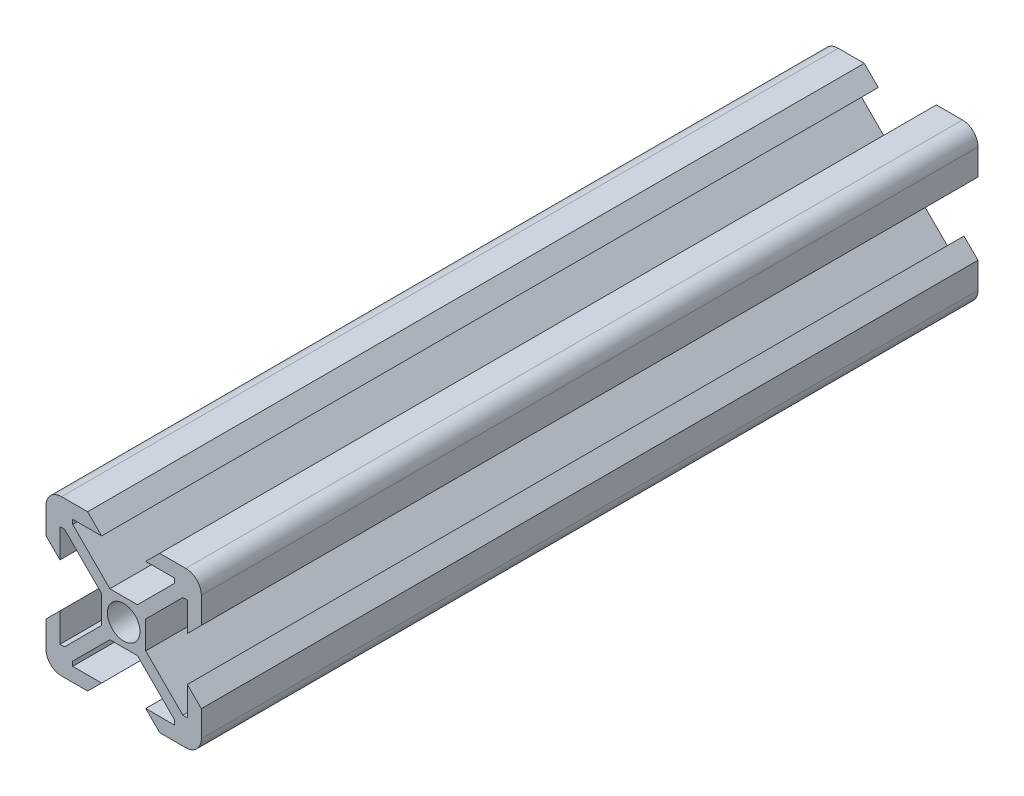
SolidWorks part; units mm, degrees
ref_plane "Front Plane" through (0, 0, 0) normal (0, 0, 1) x (1, 0, 0)
ref_plane "Top Plane" through (0, 0, 0) normal (0, 1, 0) x (1, 0, 0)
ref_plane "Right Plane" through (0, 0, 0) normal (1, 0, 0) x (0, 0, -1)
sketch "Sketch1" plane through (0, 0, 0) normal (0, 0, 1) x (1, 0, 0)
  line L0 (0, 10) -> (0, -2.84) construction
  line L1 (8, 10) -> (4.64, 10)
  line L2 (10, 4.64) -> (8.2, 2.84)
  line L3 (8.2, 2.84) -> (8.2, 6.56)
  line L4 (8.2, 6.56) -> (6.56, 6.56)
  line L5 (6.56, 6.56) -> (2.84, 2.84)
  line L6 (10, 4.64) -> (10, 8)
  line L7 (2.84, -2.84) -> (-2.84, -2.84)
  line L8 (2.84, -2.84) -> (2.84, 2.84)
  line L9 (2.84, 2.84) -> (-2.84, 2.84)
  line L10 (-2.84, -2.84) -> (-2.84, 2.84)
  line L11 (2.84, -2.84) -> (-2.84, 2.84) construction
  line L12 (2.84, 2.84) -> (-2.84, -2.84) construction
  line L13 (-4.64, 10) -> (-2.84, 8.2)
  line L14 (-2.84, 8.2) -> (-6.56, 8.2)
  line L15 (-6.56, 8.2) -> (-6.56, 6.56)
  line L16 (-6.56, 6.56) -> (-2.84, 2.84)
  line L17 (6.56, 6.56) -> (2.84, 2.84)
  line L18 (6.56, 8.2) -> (6.56, 6.56)
  line L19 (2.84, 8.2) -> (6.56, 8.2)
  line L20 (4.64, 10) -> (2.84, 8.2)
  line L21 (-4.64, 10) -> (-8, 10)
  line L22 (6.56, -6.56) -> (2.84, -2.84)
  line L23 (8.2, -6.56) -> (6.56, -6.56)
  line L24 (8.2, -2.84) -> (8.2, -6.56)
  line L25 (10, -4.64) -> (8.2, -2.84)
  line L26 (10, -8) -> (10, -4.64)
  line L27 (4.64, -10) -> (2.84, -8.2)
  line L28 (2.84, -8.2) -> (6.56, -8.2)
  line L29 (6.56, -8.2) -> (6.56, -6.56)
  line L30 (6.56, -6.56) -> (2.84, -2.84)
  line L31 (4.64, -10) -> (8, -10)
  line L32 (-6.56, -6.56) -> (-2.84, -2.84)
  line L33 (-6.56, -8.2) -> (-6.56, -6.56)
  line L34 (-2.84, -8.2) -> (-6.56, -8.2)
  line L35 (-4.64, -10) -> (-2.84, -8.2)
  line L36 (-8, -10) -> (-4.64, -10)
  line L37 (-10, -4.64) -> (-8.2, -2.84)
  line L38 (-8.2, -2.84) -> (-8.2, -6.56)
  line L39 (-8.2, -6.56) -> (-6.56, -6.56)
  line L40 (-6.56, -6.56) -> (-2.84, -2.84)
  line L41 (-10, -4.64) -> (-10, -8)
  line L42 (-6.56, 6.56) -> (-2.84, 2.84)
  line L43 (-8.2, 6.56) -> (-6.56, 6.56)
  line L44 (-8.2, 2.84) -> (-8.2, 6.56)
  line L45 (-10, 4.64) -> (-8.2, 2.84)
  line L46 (-10, 8) -> (-10, 4.64)
  line L47 (-7.6207, 6.56) -> (-2.84, 1.7793)
  line L48 (-6.56, 7.6207) -> (-1.7793, 2.84)
  line L49 (6.56, 7.6207) -> (1.7793, 2.84)
  line L50 (7.6207, 6.56) -> (2.84, 1.7793)
  line L51 (-2.84, 0) -> (2.84, 0) construction
  line L52 (7.6207, -6.56) -> (2.84, -1.7793)
  line L53 (6.56, -7.6207) -> (1.7793, -2.84)
  line L54 (-6.56, -7.6207) -> (-1.7793, -2.84)
  line L55 (-7.6207, -6.56) -> (-2.84, -1.7793)
  circle A0 centre (0, 0) radius 2.1
  arc A1 (-10, -8) -> (-8, -10) centre (-8, -8) ccw
  arc A2 (8, -10) -> (10, -8) centre (8, -8) ccw
  arc A3 (10, 8) -> (8, 10) centre (8, 8) ccw
  arc A4 (-10, 8) -> (-8, 10) centre (-8, 8) cw
  point P0 (0, 0)
  point P6 (0, 0)
  point P61 (0, 0)
  point P78 (-10, 10)
  dimension "D3" = 4.2
  dimension "D8" = 2
  dimension "D1" = 0.75
  dimension "D2" = 5.68
  dimension "D4" = 4
  dimension "D5" = 45
  dimension "D6" = 1.64
  dimension "D7" = 1.8
  dimension "D9" = 10
extrude "Boss-Extrude1" add sketch "Sketch1" along normal blind 100 contours L10 L7 L8 L9 A0 | A4 L46 L45 L44 L43 L15 L14 L13 L21 | L6 A3 L1 L20 L19 L18 L4 L3 L2 | L41 A1 L36 L35 L34 L33 L39 L38 L37 | L31 A2 L26 L25 L24 L23 L29 L28 L27 | L23 L52 L8 L22 | L53 L29 L22 L7 | L33 L54 L7 L32 | L55 L39 L32 L10 | L43 L47 L10 L16 | L48 L15 L16 L9 | L18 L49 L9 L5 | L50 L4 L5 L8 region at (7.6388, 7.6388, 0) region at (4.4238, 4.9762, 0) region at (4.9762, 4.4238, 0) region at (2.3097, 2.7597, 0) region at (-4.4238, 4.9762, 0) region at (-4.9762, 4.4238, 0) region at (-7.6388, 7.6388, 0) region at (4.9762, -4.4238, 0) region at (4.4238, -4.9762, 0) region at (7.6388, -7.6388, 0) region at (-4.9762, -4.4238, 0) region at (-4.4238, -4.9762, 0) region at (-7.6388, -7.6388, 0)
